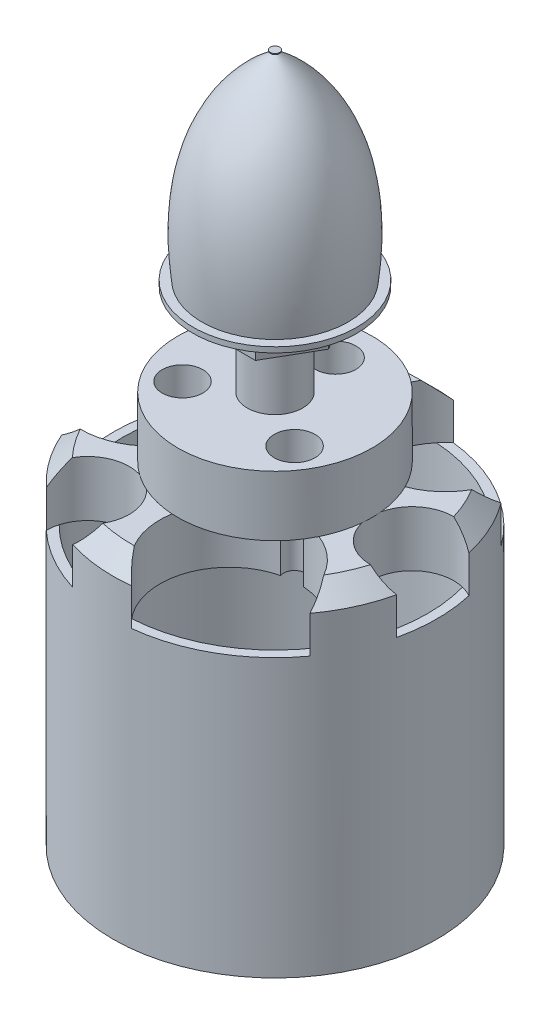
SolidWorks part; units mm, degrees
ref_plane "Ön Düzlem" through (0, 0, 0) normal (0, 0, 1) x (1, 0, 0)
ref_plane "Üst Düzlem" through (0, 0, 0) normal (0, 1, 0) x (1, 0, 0)
ref_plane "Sağ Düzlem" through (0, 0, 0) normal (1, 0, 0) x (0, 0, -1)
sketch "Çizim1" plane through (0, 0, 0) normal (0, 1, 0) x (1, 0, 0)
  circle A0 centre (0, 0) radius 16.5
  circle A1 centre (0, 0) radius 17.5
  dimension "D1" = 35
  dimension "D2" = 33
extrude "Yükseklik-Ekstrüzyon1" add sketch "Çizim1" against normal blind 30
sketch "Çizim3" plane through (0, 0, 0) normal (0, 0, 1) x (1, 0, 0)
  line L0 (0, 0) -> (17.5, 0)
  line L1 (17.5, 0) -> (-17.5, 0) construction
  line L2 (17.5, 0) -> (17.5, 4)
  line L3 (17.5, 4) -> (15.5, 6)
  line L4 (15.5, 6) -> (5.4, 6)
  line L5 (5.4, 6) -> (5.4, 8)
  line L6 (5.4, 8) -> (0, 8)
  line L7 (0, 8) -> (0, 0)
  dimension "D1" = 6
  dimension "D2" = 2
  dimension "D3" = 2
  dimension "D4" = 45
  dimension "D5" = 5.4
revolve "Döndür1" add sketch "Çizim3" angle 360 about L7
sketch "Çizim4" plane through (0, 8, 0) normal (0, 1, 0) x (1, 0, 0)
  line L0 (-17.5, 0) -> (17.5, 0) construction
  circle A0 centre (0, 0) radius 7 construction
  circle A1 centre (0, 0) radius 17.5 construction
  circle A2 centre (7, 0) radius 1
  circle A3 centre (-3.5, -6.0622) radius 1
  circle A4 centre (-3.5, 6.0622) radius 1
  point P17 (0, 0)
  dimension "D1" = 14
  dimension "D2" = 2
  dimension "D3" = 3
extrude "Kes-Ekstrüzyon1" cut sketch "Çizim4" against normal blind 30
sketch "Çizim5" plane through (0, 8, 0) normal (0, 1, 0) x (1, 0, 0)
  line L0 (-17.5, 0) -> (17.5, 0) construction
  circle A0 centre (0, 0) radius 17.5 construction
  circle A1 centre (14.83, 0) radius 4.5
  circle A2 centre (7, 0) radius 1 construction
  circle A3 centre (-7.415, -12.8432) radius 4.5
  circle A4 centre (-7.415, 12.8432) radius 4.5
  point P15 (0, 0)
  dimension "D1" = 9
  dimension "D2" = 7.83
  dimension "D3" = 3
extrude "Kes-Ekstrüzyon2" cut sketch "Çizim5" against normal blind 8
sketch "Çizim6" plane through (0, 8, 0) normal (0, 1, 0) x (1, 0, 0)
  line L0 (-8.75, -15.1554) -> (8.75, 15.1554) construction
  arc A0 (17.0576, 3.91) -> (-5.1427, 16.7273) centre (0, 0) ccw construction
  arc A1 (-11.9149, -12.8174) -> (-5.1427, -16.7273) centre (0, 0) ccw construction
  circle A2 centre (6.74, 11.674) radius 7.5
  circle A3 centre (6.74, -11.674) radius 7.5
  circle A4 centre (-13.48, 0) radius 7.5
  point P5 (0, 0)
  point P19 (0, 0)
  dimension "D1" = 15
  dimension "D2" = 13.48
  dimension "D3" = 3
extrude "Kes-Ekstrüzyon3" cut sketch "Çizim6" against normal blind 8
sketch "Çizim8" plane through (0, 6, 0) normal (0, 1, 0) x (1, 0, 0)
  circle A0 centre (0, 0) radius 10.5
  dimension "D1" = 21
extrude "Yükseklik-Ekstrüzyon3" add sketch "Çizim8" along normal blind 6.5
sketch "Çizim9" plane through (0, 12.5, 0) normal (0, 1, 0) x (1, 0, 0)
  circle A0 centre (0, 0) radius 3
  dimension "D1" = 6
extrude "Yükseklik-Ekstrüzyon4" add sketch "Çizim9" along normal blind 23.5
sketch "Çizim11" plane through (0, 12.5, 0) normal (0, 1, 0) x (1, 0, 0)
  line L0 (-6, -4) -> (6.12, -4) construction
  line L1 (6.12, -4) -> (0.06, 6.4962) construction
  line L2 (0.06, 6.4962) -> (-6, -4) construction
  circle A0 centre (0, 0) radius 10.5 construction
  point P4 (0.06, -4)
  dimension "D1" = 12.12
  dimension "D2" = 12.12
  dimension "D3" = 4
  dimension "D4" = 6
sketch "Çizim13" plane through (0, 12.5, 0) normal (0, 1, 0) x (1, 0, 0)
  circle A0 centre (0.06, 6.4962) radius 1.2
  circle A1 centre (6.12, -4) radius 1.2
  circle A2 centre (-6, -4) radius 1.2
  dimension "D1" = 2.4
extrude "Kes-Ekstrüzyon4" cut sketch "Çizim13" against normal blind 23.5
sketch "Çizim14" plane through (0, 12.5, 0) normal (0, 1, 0) x (1, 0, 0)
  circle A0 centre (0.06, 6.4962) radius 2.2
  circle A1 centre (6.12, -4) radius 2.2
  circle A2 centre (-6, -4) radius 2.2
  dimension "D1" = 4.4
extrude "Kes-Ekstrüzyon5" cut sketch "Çizim14" against normal blind 3.5
sketch "Çizim15" plane through (0, 12.5, 0) normal (0, 1, 0) x (1, 0, 0)
  line L1 (2.8868, 5) -> (-2.8868, 5)
  line L2 (-2.8868, 5) -> (-5.7735, 0)
  line L3 (-5.7735, 0) -> (-2.8868, -5)
  line L4 (-2.8868, -5) -> (2.8868, -5)
  line L5 (2.8868, -5) -> (5.7735, 0)
  line L6 (5.7735, 0) -> (2.8868, 5)
  circle A0 centre (0, 0) radius 5 construction
  dimension "D1" = 10
extrude "Yükseklik-Ekstrüzyon5" add sketch "Çizim15" along normal blind 5 from offset 6.9
sketch "Çizim17" plane through (0, 0, 0) normal (0, 0, 1) x (1, 0, 0)
  line L0 (-10.1933, 23) -> (16.4679, 23) construction
  line L1 (-2.8868, 19.4) -> (2.8868, 19.4) construction
  line L2 (0, 21.9) -> (0, 44.45)
  line L3 (0, 21.9) -> (6.55, 21.9)
  line L4 (6.55, 21.9) -> (8.8622, 22.42)
  line L5 (8.8622, 22.42) -> (8.8622, 23)
  line L6 (8.8622, 23) -> (7.9022, 23)
  spline S0 degree 2 poles (7.9022, 23) (9.6962, 38.0366) (0, 44.45) knots 0 0 0 1 1 1
  point P12 (8.6696, 23)
  point P13 (0, 0)
  dimension "D2" = 1.1
  dimension "D1" = 3.6
  dimension "D3" = 22.55
  dimension "D4" = 0.58
  dimension "D5" = 2.37
  dimension "D6" = 6.55
  dimension "D7" = 0.96
revolve "Döndür2" add sketch "Çizim17" angle 360 about L2
sketch "Çizim18" plane through (0, 12.5, 0) normal (0, 1, 0) x (1, 0, 0)
  circle A0 centre (0, 0) radius 0.5
  dimension "D1" = 1
extrude "Yükseklik-Ekstrüzyon6" add sketch "Çizim18" along normal blind 0.1 from offset 31.95 separate body
